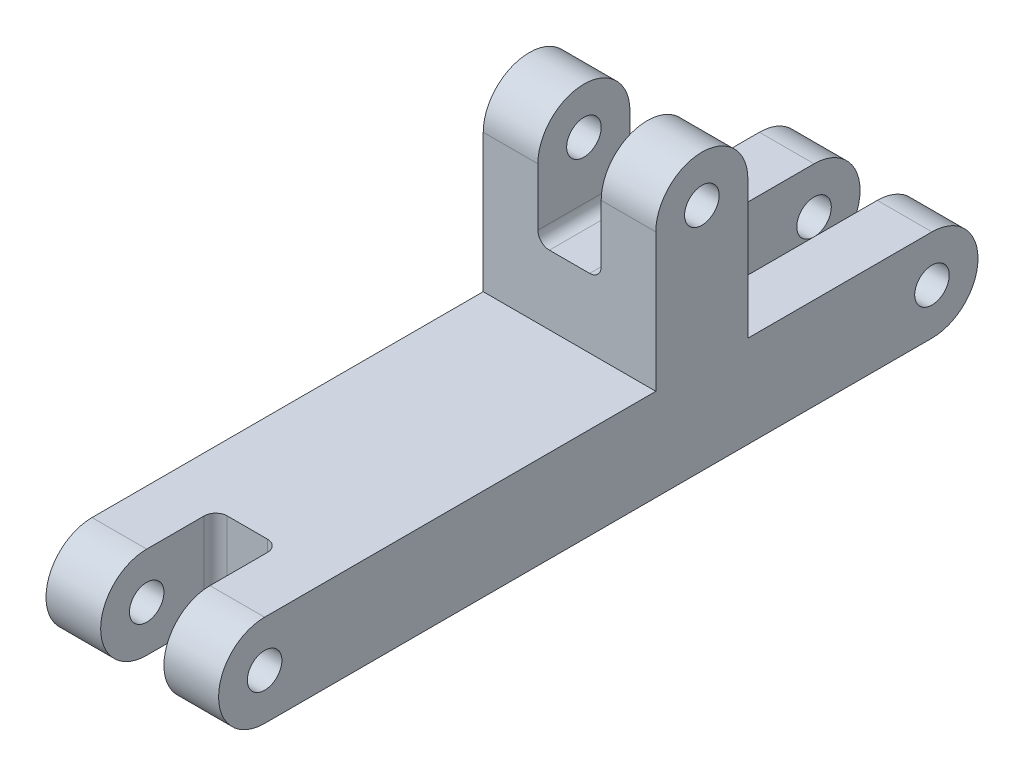
SolidWorks part; units mm, degrees
ref_plane "Alzado" through (0, 0, 0) normal (0, 0, 1) x (1, 0, 0)
ref_plane "Planta" through (0, 0, 0) normal (0, 1, 0) x (1, 0, 0)
ref_plane "Vista lateral" through (0, 0, 0) normal (1, 0, 0) x (0, 0, -1)
sketch "Croquis1" plane through (0, 0, 0) normal (1, 0, 0) x (0, 0, -1)
  line L0 (-8, 0) -> (8, 0) construction
  line L1 (-8, 4) -> (-16, 4) construction
  line L2 (-8, -4) -> (8, -4)
  line L3 (-8, 4) -> (8, 4)
  line L5 (-16, 4) -> (-16, 16)
  line L6 (-16, 16) -> (-8, 16) construction
  line L7 (-8, 4) -> (-8, 16)
  line L8 (-16, 4) -> (-50, 4)
  line L9 (-8, -4) -> (-50, -4)
  line L10 (-50, 4) -> (-50, -4) construction
  arc A0 (-8, 4) -> (-8, -4) centre (-8, 0) ccw construction
  arc A1 (8, -4) -> (8, 4) centre (8, 0) ccw
  circle A2 centre (8, 0) radius 1.5
  arc A3 (-8, 16) -> (-16, 16) centre (-12, 16) ccw
  circle A4 centre (-12, 16) radius 1.5
  circle A5 centre (-8, 0) radius 1.5 construction
  arc A6 (-50, 4) -> (-50, -4) centre (-50, 0) ccw
  circle A7 centre (-50, 0) radius 1.5
  point P3 (0, 0)
  dimension "D2" = 4
  dimension "D3" = 3
  dimension "D4" = 4
  dimension "D7" = 34
  dimension "D1" = 16
  dimension "D6" = 12
extrude "Saliente-Extruir1" add sketch "Croquis1" along normal mid plane 15
sketch "Croquis2" plane through (0, 0, 0) normal (1, 0, 0) x (0, 0, -1)
  line L0 (-16, 16) -> (-16, 4) construction
  line L1 (-16, 10) -> (-8, 10)
  line L2 (-16, 10) -> (-16, 20)
  line L3 (-16, 20) -> (-8, 20)
  line L4 (-8, 10) -> (-8, 20)
  line L5 (-8, 4) -> (-8, 16) construction
  line L11 (-50, -4) -> (8, -4) construction
  line L12 (8, 4) -> (-8, 4) construction
  line L13 (-4, 4) -> (12, 4)
  line L14 (-4, 4) -> (-4, -4)
  line L15 (-4, -4) -> (12, -4)
  line L16 (12, 4) -> (12, -4)
  line L18 (-44, 4) -> (-54, 4)
  line L19 (-44, 4) -> (-44, -4)
  line L20 (-44, -4) -> (-54, -4)
  line L21 (-54, 4) -> (-54, -4)
  line L22 (-50, -4) -> (8, -4) construction
  line L23 (-16, 4) -> (-50, 4) construction
  arc A0 (-8, 16) -> (-16, 16) centre (-12, 16) ccw construction
  arc A2 (8, -4) -> (8, 4) centre (8, 0) ccw construction
  arc A5 (-50, 4) -> (-50, -4) centre (-50, 0) ccw construction
  dimension "D5" = 10
  dimension "D1" = 10
  dimension "D3" = 16
extrude "Cortar-Extruir1" cut sketch "Croquis2" against normal mid plane 5.5
fillet "Redondeo1" radius 1 6 edges at (2.75, 0, 44) (-2.75, 0, 44) (2.75, 0, 4) (-2.75, 0, 4) (2.75, 10, 12) (-2.75, 10, 12)
